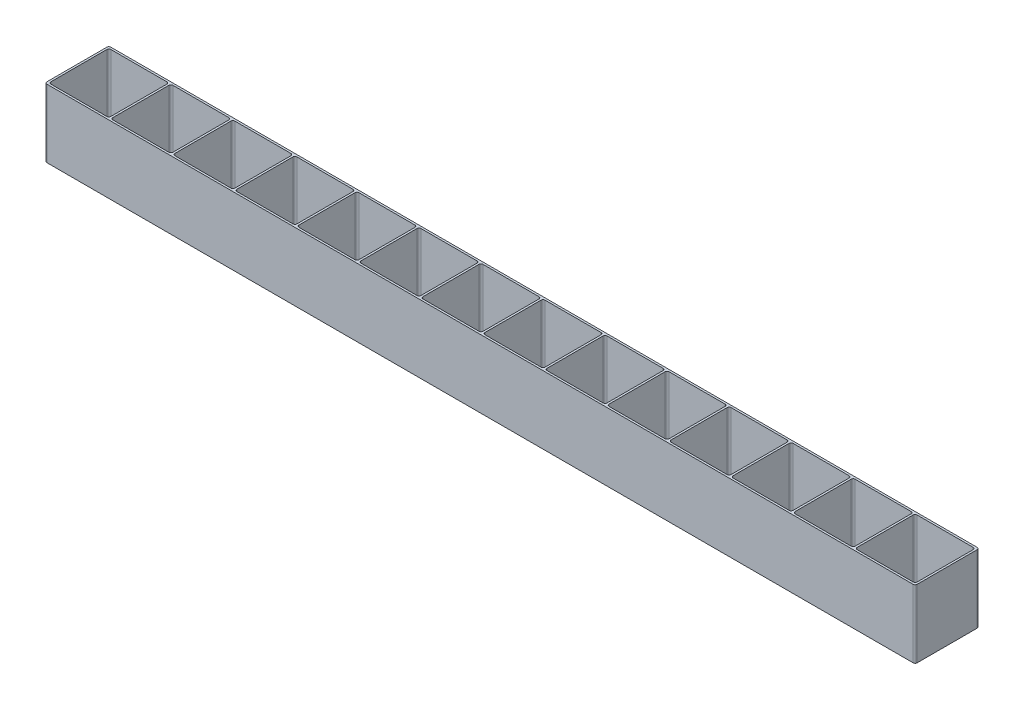
SolidWorks part; units mm, degrees
ref_plane "Front Plane" through (0, 0, 0) normal (0, 0, 1) x (1, 0, 0)
ref_plane "Top Plane" through (0, 0, 0) normal (0, 1, 0) x (1, 0, 0)
ref_plane "Right Plane" through (0, 0, 0) normal (1, 0, 0) x (0, 0, -1)
sketch "Sketch1" plane through (0, 0, 0) normal (0, 0, 1) x (1, 0, 0)
  line L1 (-435, -34) -> (435, -34)
  line L2 (-435, -34) -> (-435, 34)
  line L3 (-435, 34) -> (435, 34)
  line L4 (435, -34) -> (435, 34)
  line L5 (-435, -34) -> (435, 34) construction
  line L6 (-435, 34) -> (435, -34) construction
  point P0 (0, 0)
  dimension "D1" = 68
  dimension "25" = 870
extrude "Boss-Extrude1" add sketch "Sketch1" along normal blind 64
sketch "Sketch2" plane through (0, 34, 0) normal (0, 1, 0) x (1, 0, 0)
  line L0 (-435, -32) -> (435, -32) construction
  line L5 (-435, -64) -> (-435, 0) construction
  line L6 (435, -64) -> (435, 0) construction
  line L8 (-433, -62) -> (-373, -62)
  line L9 (-433, -62) -> (-433, -2)
  line L10 (-433, -2) -> (-373, -2)
  line L11 (-373, -62) -> (-373, -2)
  line L12 (-433, -62) -> (-373, -2) construction
  line L13 (-433, -2) -> (-373, -62) construction
  point P6 (-403, -32)
  dimension "D1" = 60
  dimension "D2" = 60
  dimension "D3" = 2
extrude "Cut-Extrude1" cut sketch "Sketch2" against normal blind 65
fillet "Fillet2" radius 2 4 edges at (-433, 1.5, 62) (-373, 1.5, 62) (-433, 1.5, 2) (-373, 1.5, 2)
fillet "Fillet1" radius 2 4 edges at (-435, 0, 64) (-435, 0, 0) (435, 0, 64) (435, 0, 0)
pattern_linear "LPattern2" count 14 spacing 62 along (1, 0, 0) of "Cut-Extrude1", "Fillet2"
